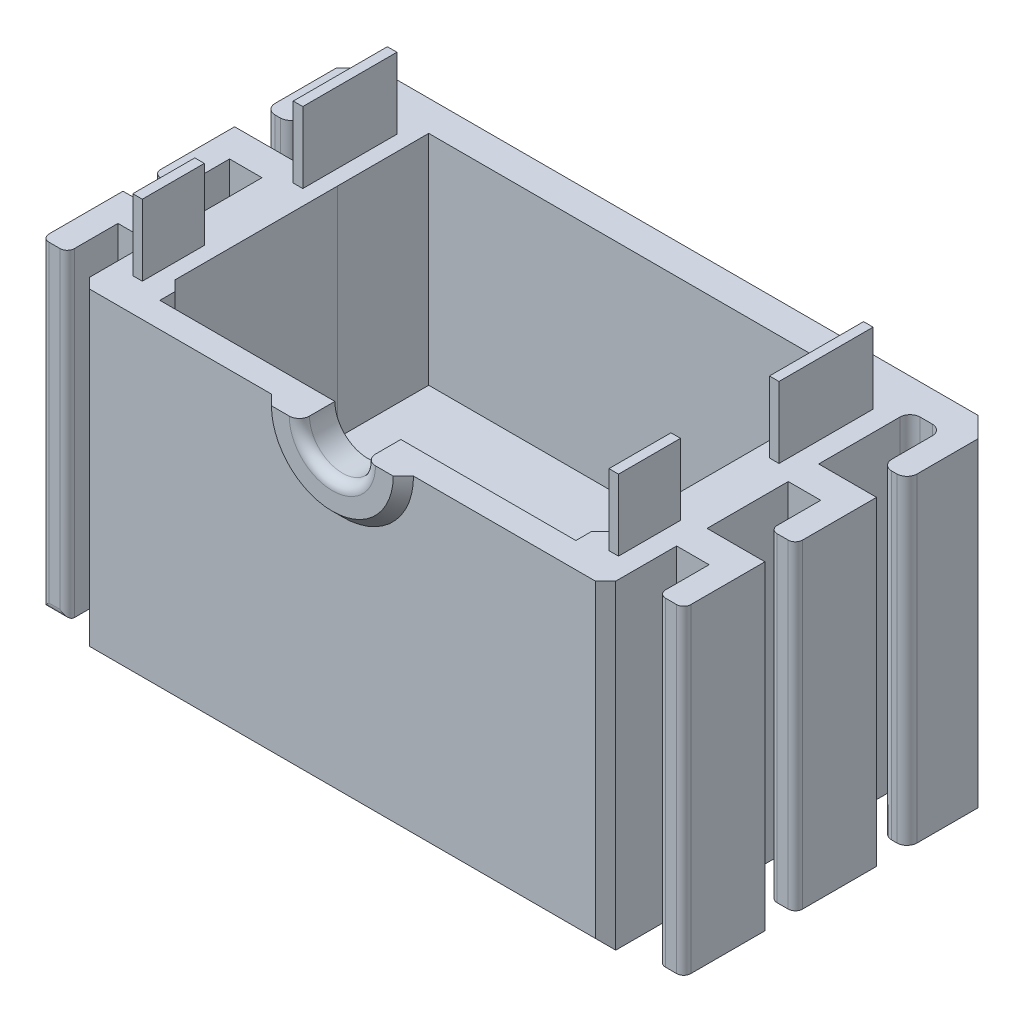
SolidWorks part; units mm, degrees
ref_plane "Plan de face" through (0, 0, 0) normal (0, 0, 1) x (1, 0, 0)
ref_plane "Plan de dessus" through (0, 0, 0) normal (0, 1, 0) x (1, 0, 0)
ref_plane "Plan de droite" through (0, 0, 0) normal (1, 0, 0) x (0, 0, -1)
sketch "Esquisse1" plane through (0, 0, 0) normal (0, 0, 1) x (1, 0, 0)
  line L1 (0, 0) -> (51.86, 0)
  line L2 (0, 0) -> (0, 63)
  line L3 (0, 63) -> (51.86, 63)
  line L4 (51.86, 0) -> (51.86, 63)
  dimension "D1" = 63
  dimension "D2" = 51.86
extrude "Boss.-Extru.1" add sketch "Esquisse1" along normal blind 20
sketch "Esquisse2" plane through (0, 0, 0) normal (0, 0, -1) x (-1, 0, 0)
  line L0 (-51.86, 63) -> (0, 0)
  line L2 (-47.43, 10) -> (-4.43, 10)
  line L3 (-47.43, 10) -> (-47.43, 53)
  line L4 (-47.43, 53) -> (-4.43, 53)
  line L5 (-4.43, 10) -> (-4.43, 53)
  line L6 (-47.43, 10) -> (-4.43, 53) construction
  line L7 (-47.43, 53) -> (-4.43, 10) construction
  point P4 (-25.93, 31.5)
extrude "Enlèv. mat.-Extru.1" cut sketch "Esquisse2" against normal blind 18 contours L4 L3 L2 L0 | L2 L5 L4 L0 region at (17.6081, 37.3994, 0) region at (34.2519, 25.6006, 0)
sketch "Esquisse3" plane through (0, 0, 0) normal (0, 0, -1) x (-1, 0, 0)
  line L0 (-25.93, 63) -> (-25.93, 0)
  line L1 (-51.86, 63) -> (0, 63) construction
  line L2 (0, 0) -> (-51.86, 0) construction
  line L3 (-4.53, 55.9) -> (-13.23, 55.9)
  line L4 (-51.86, 63) -> (-47.33, 63)
  line L5 (-51.86, 63) -> (-51.86, 58.9)
  line L6 (-51.86, 58.9) -> (-47.33, 58.9)
  line L7 (-47.33, 63) -> (-47.33, 58.9)
  line L8 (-47.33, 58.9) -> (-38.63, 58.9)
  line L9 (-47.33, 58.9) -> (-47.33, 55.9)
  line L10 (-47.33, 55.9) -> (-38.63, 55.9)
  line L11 (-38.63, 58.9) -> (-38.63, 55.9)
  line L12 (-13.23, 58.9) -> (-13.23, 55.9)
  line L13 (-4.53, 58.9) -> (-13.23, 58.9)
  line L14 (-4.53, 58.9) -> (-4.53, 55.9)
  line L15 (0, 31.5) -> (-25.93, 31.5)
  line L16 (0, 63) -> (0, 0) construction
  line L17 (-4.53, 4.1) -> (-4.53, 7.1)
  line L18 (-4.53, 4.1) -> (-13.23, 4.1)
  line L19 (-13.23, 4.1) -> (-13.23, 7.1)
  line L20 (-4.53, 7.1) -> (-13.23, 7.1)
  line L21 (-47.33, 7.1) -> (-38.63, 7.1)
  line L22 (-38.63, 4.1) -> (-38.63, 7.1)
  line L23 (-47.33, 4.1) -> (-38.63, 4.1)
  line L24 (-47.33, 4.1) -> (-47.33, 7.1)
  dimension "D1" = 4.1
  dimension "D2" = 4.53
  dimension "D3" = 8.7
  dimension "D4" = 3
extrude "Boss.-Extru.2" add sketch "Esquisse3" along normal blind 7 contours L14 L13 L12 L3 | L11 L8 L9 L10 | L24 L23 L22 L21 | L17 L20 L19 L18 region at (8.88, 57.4, 0) region at (42.98, 57.4, 0) region at (8.88, 5.6, 0) region at (42.98, 5.6, 0)
sketch "Esquisse4" plane through (0, 0, 18) normal (0, 0, -1) x (-1, 0, 0)
  line L1 (-47.43, 53) -> (-4.43, 53)
  line L2 (-47.43, 53) -> (-47.43, 10)
  line L3 (-47.43, 10) -> (-4.43, 10)
  line L4 (-4.43, 53) -> (-4.43, 10)
extrude "Boss.-Extru.3" add sketch "Esquisse4" along normal blind 1
chamfer "Chanfrein1" distance 1 angle 45 4 edges at (4.43, 10, 8.5) (47.43, 10, 8.5) (4.43, 53, 8.5) (47.43, 53, 8.5)
sketch "Esquisse6" plane through (0, 0, 17) normal (0, 0, -1) x (-1, 0, 0)
  line L0 (-25.93, 53) -> (-25.93, 10)
  line L1 (-46.43, 53) -> (-5.43, 53) construction
  line L2 (-46.43, 10) -> (-5.43, 10) construction
  circle A0 centre (-25.93, 31.5) radius 7
extrude "Boss.-Extru.4" add sketch "Esquisse6" against normal blind 5 contours A0
sketch "Esquisse7" plane through (0, 0, 17) normal (0, 0, -1) x (-1, 0, 0)
  line L0 (-25.93, 53) -> (-25.93, 10)
  line L1 (-46.43, 53) -> (-5.43, 53) construction
  line L2 (-46.43, 10) -> (-5.43, 10) construction
  circle A0 centre (-25.93, 31.5) radius 3.25
extrude "Enlèv. mat.-Extru.2" cut sketch "Esquisse7" against normal blind 10 contours L0 A0 | L0 A0 region at (24.5507, 31.5, 17) region at (27.3093, 31.5, 17)
sketch "Esquisse8" plane through (0, 63, 0) normal (0, 1, 0) x (1, 0, 0)
  line L0 (25.93, 0) -> (25.93, -20)
  line L1 (51.86, 0) -> (0, 0) construction
  line L2 (51.86, -20) -> (0, -20) construction
  line L3 (55.06, -9) -> (55.06, -3)
  line L4 (0, 0) -> (-5.7, 0)
  line L5 (0, 0) -> (0, -9)
  line L6 (0, -9) -> (-5.7, -9)
  line L7 (-5.7, 0) -> (-5.7, -9)
  line L8 (0, -20) -> (-5.7, -20)
  line L9 (0, -20) -> (0, -11)
  line L10 (0, -11) -> (-5.7, -11)
  line L11 (-5.7, -20) -> (-5.7, -11)
  line L12 (0, -20) -> (-3.2, -20)
  line L13 (0, -20) -> (0, -14)
  line L14 (0, -14) -> (-3.2, -14)
  line L15 (-3.2, -20) -> (-3.2, -14)
  line L16 (0, -9) -> (-3.2, -9)
  line L17 (0, -9) -> (0, -3)
  line L18 (0, -3) -> (-3.2, -3)
  line L19 (-3.2, -9) -> (-3.2, -3)
  line L20 (51.86, -9) -> (57.56, -9)
  line L21 (57.56, 0) -> (57.56, -9)
  line L22 (51.86, 0) -> (57.56, 0)
  line L23 (51.86, 0) -> (51.86, -9)
  line L24 (51.86, -14) -> (55.06, -14)
  line L25 (55.06, -20) -> (55.06, -14)
  line L26 (51.86, -11) -> (57.56, -11)
  line L27 (57.56, -20) -> (57.56, -11)
  line L28 (51.86, -20) -> (57.56, -20)
  line L29 (51.86, -20) -> (51.86, -11)
  line L30 (51.86, -3) -> (55.06, -3)
  line M21 (0, 0) -> (0, -20)
  line M23 (51.86, -20) -> (51.86, 0)
extrude "Boss.-Extru.5" add sketch "Esquisse8" against normal up to surface (63 mm away) contours L23 L30 L3 L20 L21 L22 | L25 L28 L27 L26 L24 M23 | L6 L19 L18 L4 L7 M21 | L8 L15 L14 L10 L11 M21 region at (55.4577, 63, 14.6028) region at (55.4577, 63, 3.6028) region at (-3.5977, 63, 3.6028) region at (-3.5977, 63, 14.6028) up to face at (25.93, 0, 10)
sketch "Esquisse9" plane through (0, 0, 0) normal (0, -1, 0) x (1, 0, 0)
  line L0 (25.93, 20) -> (25.93, 0)
  line L1 (0, 20) -> (51.86, 20) construction
  line L2 (-5.7, 0) -> (57.56, 0) construction
  line L3 (-3.2, 14) -> (-3.2, 20) construction
  line L4 (-5.7, 20) -> (-3.2, 20)
  line L5 (-5.7, 20) -> (-5.7, 19)
  line L6 (-5.7, 19) -> (-3.2, 19)
  line L7 (-3.2, 20) -> (-3.2, 19)
  line L8 (-3.2, 3) -> (-3.2, 9) construction
  line L9 (-5.7, 9) -> (-3.2, 9)
  line L10 (-5.7, 9) -> (-5.7, 8)
  line L11 (-5.7, 8) -> (-3.2, 8)
  line L12 (-3.2, 9) -> (-3.2, 8)
  line L13 (57.56, 8) -> (55.06, 8)
  line L14 (55.06, 9) -> (55.06, 8)
  line L15 (57.56, 9) -> (55.06, 9)
  line L16 (57.56, 9) -> (57.56, 8)
  line L17 (57.56, 19) -> (55.06, 19)
  line L18 (55.06, 20) -> (55.06, 19)
  line L19 (57.56, 20) -> (55.06, 20)
  line L20 (57.56, 20) -> (57.56, 19)
  line M11 (57.56, 0) -> (57.56, 9)
  line M12 (57.56, 9) -> (55.06, 9)
  line M13 (55.06, 9) -> (55.06, 3)
  line M25 (-3.2, 14) -> (-3.2, 20)
  line M26 (-3.2, 20) -> (-5.7, 20)
  line M27 (-5.7, 20) -> (-5.7, 11)
  line M31 (-3.2, 3) -> (-3.2, 9)
  line M32 (-3.2, 9) -> (-5.7, 9)
  line M33 (-5.7, 9) -> (-5.7, 0)
  dimension "D1" = 1
  dimension "D2" = 1
extrude "Enlèv. mat.-Extru.3" cut sketch "Esquisse9" against normal up to surface (63 mm away) contours L11 M33 M31 M32 | L6 M27 M25 M26 | L13 M11 M12 M13 | L17 L18 L19 L20 region at (-4.45, 0, 19.5) region at (-4.45, 0, 8.5) region at (56.31, 0, 8.5) up to face at (25.93, 63, 11.1667)
chamfer "Chanfrein3" distance 1 angle 45 9 edges at (46.93, 10.5, 17) (47.43, 31.5, 17) (46.93, 52.5, 17) (25.93, 53, 17) (4.93, 52.5, 17) (4.43, 31.5, 17) (4.93, 10.5, 17) (25.93, 10, 17) (22.68, 31.5, 17)
fillet "Congé1" radius 1 16 edges at (8.88, 4.1, -7) (13.23, 5.6, -7) (8.88, 7.1, -7) (4.53, 5.6, -7) (42.98, 7.1, -7) (38.63, 5.6, -7) (42.98, 4.1, -7) (47.33, 5.6, -7) (8.88, 55.9, -7) (13.23, 57.4, -7) (8.88, 58.9, -7) (4.53, 57.4, -7) (42.98, 55.9, -7) (47.33, 57.4, -7) (42.98, 58.9, -7) (38.63, 57.4, -7)
fillet "Congé2" radius 1 1 edges at (22.68, 31.5, 22)
fillet "Congé5" radius 0.7 10 edges at (-3.2, 31.5, 19) (-5.7, 31.5, 19) (-3.2, 31.5, 8) (-5.7, 31.5, 8) (55.06, 31.5, 8) (57.56, 31.5, 8) (55.06, 31.5, 19) (57.56, 31.5, 19) (-4.45, 0, 19) (-4.45, 63, 19)
ref_plane "Plan1" through (5.53, 5.1, -7) normal (-1, 0, 0) x (0, 0, 1)
sketch "Esquisse19" plane through (0, 0, 17) normal (0, 0, -1) x (-1, 0, 0)
  line L0 (-46.43, 11.4142) -> (-46.0158, 11)
  line L1 (-46.0158, 11) -> (-5.8442, 11)
  line L2 (-5.8442, 11) -> (-5.43, 11.4142)
  line L3 (-5.43, 11.4142) -> (-5.43, 51.5858)
  line L4 (-5.43, 51.5858) -> (-5.8442, 52)
  line L5 (-5.8442, 52) -> (-46.0158, 52)
  line L6 (-46.0158, 52) -> (-46.43, 51.5858)
  line L7 (-46.43, 51.5858) -> (-46.43, 11.4142)
extrude "Enlèv. mat.-Extru.11" cut sketch "Esquisse19" against normal blind 1.5
sketch "Esquisse24" plane through (57.56, 0, 0) normal (1, 0, 0) x (0, 0, -1)
  line L1 (7.9339, 31.5) -> (-30.6314, 31.5)
  line L2 (7.9339, 31.5) -> (7.9339, 66.4074)
  line L3 (7.9339, 66.4074) -> (-30.6314, 66.4074)
  line L4 (-30.6314, 31.5) -> (-30.6314, 66.4074)
extrude "Enlèv. mat.-Extru.16" cut sketch "Esquisse24" against normal blind 74
sketch "Esquisse25" plane through (0, 31.5, 0) normal (0, 1, 0) x (1, 0, 0)
  line L0 (47.43, 0) -> (47.4294, 9)
  line L1 (47.43, 0) -> (47.43, -16) construction
  line L2 (47.4294, 9) -> (4.4294, 9)
  line L3 (25.9294, 12) -> (25.9294, 9)
  line L4 (-3.7013, 12) -> (55.56, 12)
  line L5 (55.56, 12) -> (57.56, 10)
  line L6 (57.56, 10) -> (57.56, 4)
  line L7 (56.56, 3) -> (56.06, 3)
  line L8 (55.06, 4) -> (55.06, 8)
  line L9 (54.06, 9) -> (52.86, 9)
  line L10 (51.86, 8) -> (51.86, 0)
  line L11 (57.56, 0) -> (47.43, 0) construction
  line L12 (51.86, 0) -> (47.43, 0)
  line L13 (-0.0013, 8) -> (-0.0013, 0)
  line L14 (-2.2013, 9) -> (-1.0013, 9)
  line L15 (-3.2013, 4) -> (-3.2013, 8)
  line L16 (-4.7013, 3) -> (-4.2013, 3)
  line L17 (-5.7013, 10) -> (-5.7013, 4)
  line L18 (-3.7013, 12) -> (-5.7013, 10)
  line L19 (4.4287, 0) -> (4.4294, 9)
  line L20 (-0.0013, 0) -> (4.4287, 0)
  arc A0 (57.56, 4) -> (56.56, 3) centre (56.56, 4) cw
  arc A1 (56.06, 3) -> (55.06, 4) centre (56.06, 4) cw
  arc A2 (55.06, 8) -> (54.06, 9) centre (54.06, 8) ccw
  arc A3 (52.86, 9) -> (51.86, 8) centre (52.86, 8) ccw
  arc A4 (-1.0013, 9) -> (-0.0013, 8) centre (-1.0013, 8) cw
  arc A5 (-3.2013, 8) -> (-2.2013, 9) centre (-2.2013, 8) cw
  arc A6 (-4.2013, 3) -> (-3.2013, 4) centre (-4.2013, 4) ccw
  arc A7 (-5.7013, 4) -> (-4.7013, 3) centre (-4.7013, 4) ccw
  line M9 (57.56, 0) -> (47.43, 0)
extrude "Boss.-Extru.11" add sketch "Esquisse25" against normal up to surface (31.5 mm away) contours A3 L9 A2 L8 A1 L7 A0 L6 L5 L4 L3 L2 L0 L10 M9 | L17 A7 L16 A6 L15 A5 L14 A4 L13 L20 L19 L2 L3 L4 L18 region at (47.768, 31.5, -4.5) region at (15.1794, 31.5, -9.3383) up to face at (27.9553, 0, 10.8423)
sketch "Esquisse26" plane through (0, 4.1, 0) normal (0, -1, 0) x (1, 0, 0)
  line L0 (47.4294, -9) -> (47.43, 0) construction
  line L1 (47.43, 0) -> (4.4293, 0)
  line L2 (47.43, 0) -> (47.43, -8.3232)
  line L3 (47.43, -8.3232) -> (4.4293, -8.3232)
  line L4 (4.4293, 0) -> (4.4293, -8.3232)
  line L5 (4.4287, 0) -> (47.43, 0) construction
  line L6 (4.4294, -9) -> (4.4287, 0) construction
extrude "Enlèv. mat.-Extru.17" cut sketch "Esquisse26" against normal blind 74
sketch "Esquisse27" plane through (0, 0, 0) normal (0, -1, 0) x (1, 0, 0)
  line L0 (47.4294, -9) -> (47.43, 0) construction
  line L1 (47.43, 0) -> (4.4294, 0)
  line L2 (47.43, 0) -> (47.43, -9)
  line L3 (47.43, -9) -> (4.4294, -9)
  line L4 (4.4294, 0) -> (4.4294, -9)
  line L5 (4.4294, -9) -> (47.4294, -9) construction
  line L6 (4.4294, -9) -> (4.4287, 0) construction
extrude "Boss.-Extru.12" add sketch "Esquisse27" against normal up to surface (10 mm away) up to face at (25.93, 10, 8)
sketch "Esquisse28" plane through (0, 0, 20) normal (0, 0, 1) x (1, 0, 0)
  line L5 (51.86, 0) -> (51.86, 31.5)
  line L6 (51.86, 31.5) -> (32.93, 31.5)
  line L7 (18.93, 31.5) -> (0, 31.5)
  line L8 (0, 31.5) -> (0, 0)
  line L9 (0, 0) -> (51.86, 0)
  line L10 (51.86, 0) -> (51.86, 31.5)
  line L11 (51.86, 31.5) -> (32.93, 31.5)
  line L12 (18.93, 31.5) -> (0, 31.5)
  line L13 (0, 31.5) -> (0, 0)
  line L14 (0, 0) -> (51.86, 0)
  arc A1 (18.93, 31.5) -> (32.93, 31.5) centre (25.93, 31.5) ccw
  arc A3 (18.93, 31.5) -> (32.93, 31.5) centre (25.93, 31.5) ccw
  dimension "D1" = 0
extrude "Boss.-Extru.13" add sketch "Esquisse28" along normal blind 1
chamfer "Chanfrein4" distance 1 angle 45 1 edges at (25.93, 24.5, 22)
chamfer "Chanfrein5" distance 1 angle 45 4 edges at (25.9294, 0, -12) (51.86, 15.75, 21) (25.93, 0, 21) (0, 15.75, 21)
sketch "Esquisse29" plane through (0, 31.5, 0) normal (0, 1, 0) x (1, 0, 0)
  line L0 (25.93, -18.5) -> (25.93, -25.4029)
  line L1 (49.8649, -17.7339) -> (48.9244, -17.7339)
  line L2 (49.8649, -17.7339) -> (49.8649, -11.6207)
  line L3 (49.8649, -11.6207) -> (48.9244, -11.6207)
  line L4 (48.9244, -17.7339) -> (48.9244, -11.6207)
  line L5 (49.8649, -1.9184) -> (48.9244, -1.9184)
  line L6 (49.8649, -1.9184) -> (49.8649, 7.3596)
  line L7 (49.8649, 7.3596) -> (48.9244, 7.3596)
  line L8 (48.9244, -1.9184) -> (48.9244, 7.3596)
  line L9 (29.18, -18.5) -> (22.68, -18.5) construction
  line L10 (2.9356, -1.9184) -> (2.9356, 7.3596)
  line L11 (1.9951, 7.3596) -> (2.9356, 7.3596)
  line L12 (1.9951, -1.9184) -> (1.9951, 7.3596)
  line L13 (2.9356, -17.7339) -> (2.9356, -11.6207)
  line L14 (1.9951, -11.6207) -> (2.9356, -11.6207)
  line L15 (1.9951, -17.7339) -> (1.9951, -11.6207)
  line L16 (1.9951, -17.7339) -> (2.9356, -17.7339)
  line L17 (1.9951, -1.9184) -> (2.9356, -1.9184)
extrude "Boss.-Extru.14" add sketch "Esquisse29" along normal blind 7 contours L15 L16 L13 L14 | L12 L17 L10 L11 | L8 L5 L6 L7 | L4 L1 L2 L3 region at (49.3946, 31.5, 14.6773) region at (49.3946, 31.5, -2.7206) region at (2.4654, 31.5, -2.7206) region at (2.4654, 31.5, 14.6773)
